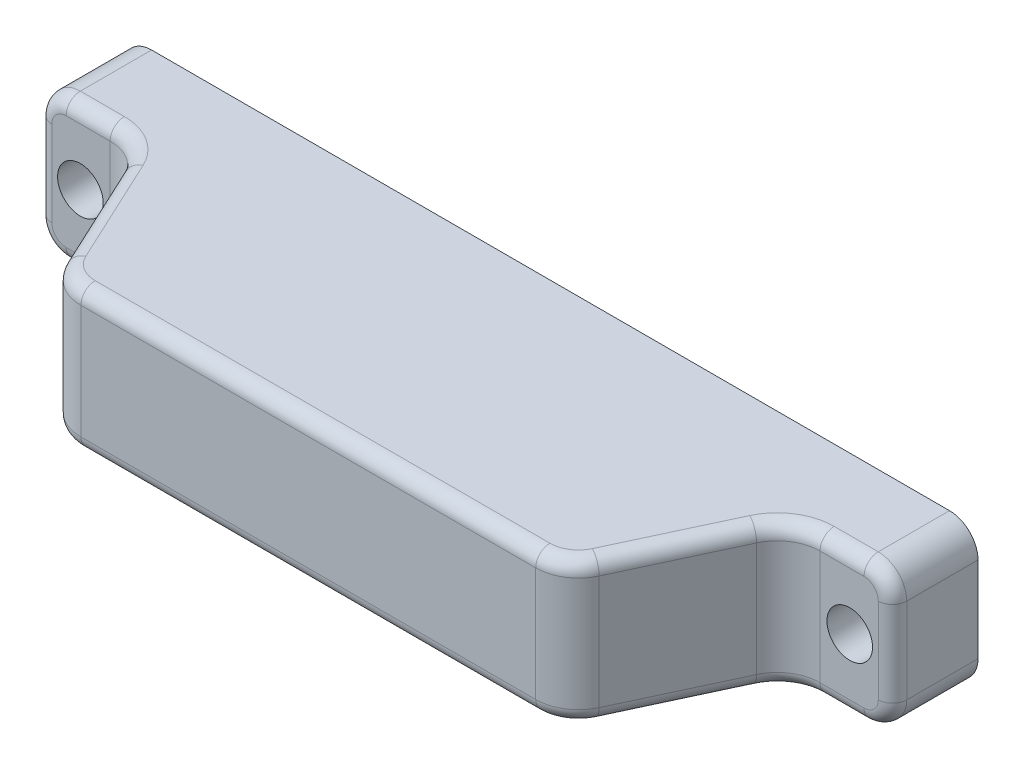
SolidWorks part; units mm, degrees
ref_plane "Front Plane" through (0, 0, 0) normal (0, 0, 1) x (1, 0, 0)
ref_plane "Top Plane" through (0, 0, 0) normal (0, 1, 0) x (1, 0, 0)
ref_plane "Right Plane" through (0, 0, 0) normal (1, 0, 0) x (0, 0, -1)
sketch "Sketch1" plane through (0, 0, 0) normal (0, 0, 1) x (1, 0, 0)
  line L1 (-119, -97.7573) -> (-59, -97.7573)
  line L2 (-119, -97.7573) -> (-119, -87.7573)
  line L3 (-119, -87.7573) -> (-59, -87.7573)
  line L4 (-59, -97.7573) -> (-59, -87.7573)
  line L7 (-89, -7.4927) -> (-89, -172.4927) construction
  dimension "D1" = 30
  dimension "D2" = 60
extrude "Boss-Extrude1" add sketch "Sketch1" along normal blind 17
sketch "Sketch2" plane through (0, -97.7573, 0) normal (0, -1, 0) x (1, 0, 0)
  line L0 (-106.8706, 17) -> (-112, 6)
  line L1 (-119, 17) -> (-59, 17) construction
  line L2 (-112, 6) -> (-119, 6)
  line L3 (-119, 17) -> (-119, 0) construction
  line L4 (-119, 0) -> (-59, 0) construction
  line L5 (-119, 6) -> (-119, 17)
  line L6 (-119, 17) -> (-106.8706, 17)
  line L7 (-89, 0) -> (-89, 17) construction
  line L8 (-104, 17) -> (-74, 17) construction
  line L9 (-59, 17) -> (-71.1294, 17)
  line L10 (-59, 6) -> (-59, 17)
  line L11 (-66, 6) -> (-59, 6)
  line L12 (-71.1294, 17) -> (-66, 6)
  dimension "D1" = 6
  dimension "D2" = 7
  dimension "D3" = 115
extrude "Cut-Extrude1" cut sketch "Sketch2" against normal up to surface (10 mm away) up to face at (-89, -87.7573, 8.5)
fillet "Fillet1" radius 3 4 edges at (-66, -92.7573, 6) (-71.1294, -92.7573, 17) (-106.8706, -92.7573, 17) (-112, -92.7573, 6)
fillet "Fillet2" radius 2 4 edges at (-119, -87.7573, 3) (-119, -97.7573, 3) (-59, -87.7573, 3) (-59, -97.7573, 3)
sketch "Sketch3" plane through (0, 0, 6) normal (0, 0, 1) x (1, 0, 0)
  circle A0 centre (-116, -92.7573) radius 1.6
  circle A1 centre (-62, -92.7573) radius 1.6
extrude "Cut-Extrude2" cut sketch "Sketch3" against normal up to surface (6 mm away) up to face at (-89, -92.7573, 0)
fillet "Fillet3" radius 1 24 edges at (-71.4287, -97.7573, 16.5302) (-89, -97.7573, 17) (-106.5713, -97.7573, 16.5302) (-109.4353, -97.7573, 11.5) (-112.2993, -97.7573, 6.4698) (-115.4556, -97.7573, 6) (-118.4142, -97.1715, 6) (-119, -92.7573, 6) (-118.4142, -88.3431, 6) (-115.4556, -87.7573, 6) (-112.2993, -87.7573, 6.4698) (-109.4353, -87.7573, 11.5) (-106.5713, -87.7573, 16.5302) (-89, -87.7573, 17) (-71.4287, -87.7573, 16.5302) (-68.5647, -87.7573, 11.5) (-65.7007, -87.7573, 6.4698) (-62.5444, -87.7573, 6) (-59.5858, -88.3431, 6) (-59, -92.7573, 6) (-59.5858, -97.1715, 6) (-62.5444, -97.7573, 6) (-65.7007, -97.7573, 6.4698) (-68.5647, -97.7573, 11.5)
